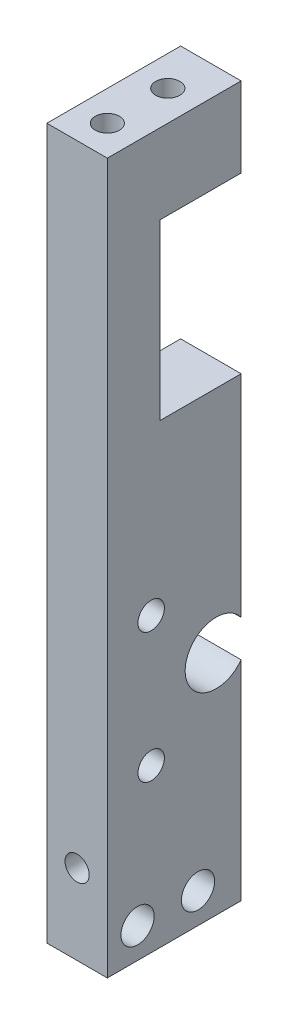
SolidWorks part; units mm, degrees
material "6061-T6 (SS)"
ref_plane "前视基准面" through (0, 0, 0) normal (0, 0, 1) x (1, 0, 0)
ref_plane "上视基准面" through (0, 0, 0) normal (0, 1, 0) x (1, 0, 0)
ref_plane "右视基准面" through (0, 0, 0) normal (1, 0, 0) x (0, 0, -1)
other "Configuration Table"
sketch "草图1" plane through (0, 0, 0) normal (0, 0, 1) x (1, 0, 0)
  line L1 (49.65, -4.3) -> (53.65, -4.3)
  line L2 (49.65, -4.3) -> (49.65, 42.68)
  line L3 (49.65, 42.68) -> (53.65, 42.68)
  line L4 (53.65, -4.3) -> (53.65, 42.68)
  dimension "D1" = 49.65
  dimension "D2" = 53.65
  dimension "D3" = 42.68
  dimension "D4" = 4.3
extrude "Main_Stock" add sketch "草图1" along normal blind 8.8519 from offset 2.2481
sketch "草图2" plane through (0, 0, 11.1) normal (0, 0, 1) x (1, 0, 0)
  circle A0 centre (51.65, 1) radius 0.8
  dimension "D1" = 1.6
  dimension "D2" = 51.65
  dimension "D3" = 1
extrude "Frame_1xD1p6_Through" cut sketch "草图2" against normal through all
cosmetic thread "Frame_M2_Through_Cosmetic_1" parameters "D2"=2
sketch "草图3" plane through (53.65, 0, 0) normal (1, 0, 0) x (0, 0, -1)
  circle A0 centre (-3.8995, 10.725) radius 2.05
  dimension "D1" = 4.1
  dimension "D2" = 3.8995
  dimension "D3" = 10.725
extrude "SMA_Center_D4p1" cut sketch "草图3" against normal blind 4
sketch "草图4" plane through (53.65, 0, 0) normal (1, 0, 0) x (0, 0, -1)
  circle A0 centre (-8.1995, 6.425) radius 0.875
  circle A1 centre (-8.1995, 15.025) radius 0.875
  dimension "D1" = 1.75
  dimension "D2" = 8.1995
  dimension "D3" = 6.425
  dimension "D4" = 15.025
extrude "SMA_Upper_2xD1p75_Through" cut sketch "草图4" against normal through all
cosmetic thread "SMA_Upper_Cosmetic_1" parameters "D2"=2.2
cosmetic thread "SMA_Upper_Cosmetic_2" parameters "D2"=2.2
sketch "草图5" plane through (53.65, 0, 0) normal (1, 0, 0) x (0, 0, -1)
  line L1 (-0.9, 25.9) -> (-7.6, 25.9)
  line L2 (-0.9, 25.9) -> (-0.9, 37.4)
  line L3 (-0.9, 37.4) -> (-7.6, 37.4)
  line L4 (-7.6, 25.9) -> (-7.6, 37.4)
  dimension "D1" = 0.9
  dimension "D2" = 7.6
  dimension "D3" = 25.9
  dimension "D4" = 37.4
extrude "TypeC_Window_11p5x6p7" cut sketch "草图5" against normal blind 4
sketch "草图6" plane through (53.65, 0, 0) normal (1, 0, 0) x (0, 0, -1)
  circle A0 centre (-5.1, -2.3) radius 1.1
  circle A1 centre (-9.1, -2.3) radius 1.1
  dimension "D1" = 2.2
  dimension "D2" = 5.1
  dimension "D3" = 9.1
  dimension "D4" = 2.3
extrude "Corner_Front_2xD2p2_Through" cut sketch "草图6" against normal through all
sketch "草图7" plane through (0, 42.68, 0) normal (0, 1, 0) x (1, 0, 0)
  circle A0 centre (51.65, -5.1) radius 0.8
  circle A1 centre (51.65, -9.1) radius 0.8
  dimension "D1" = 1.6
  dimension "D2" = 51.65
  dimension "D3" = 5.1
  dimension "D4" = 9.1
extrude "Corner_Rear_2xD1p6_Blind4" cut sketch "草图7" against normal blind 4
cosmetic thread "Corner_Rear_M2_Cosmetic_1" parameters "D1"=3.5, "D2"=2
cosmetic thread "Corner_Rear_M2_Cosmetic_2" parameters "D1"=3.5, "D2"=2
